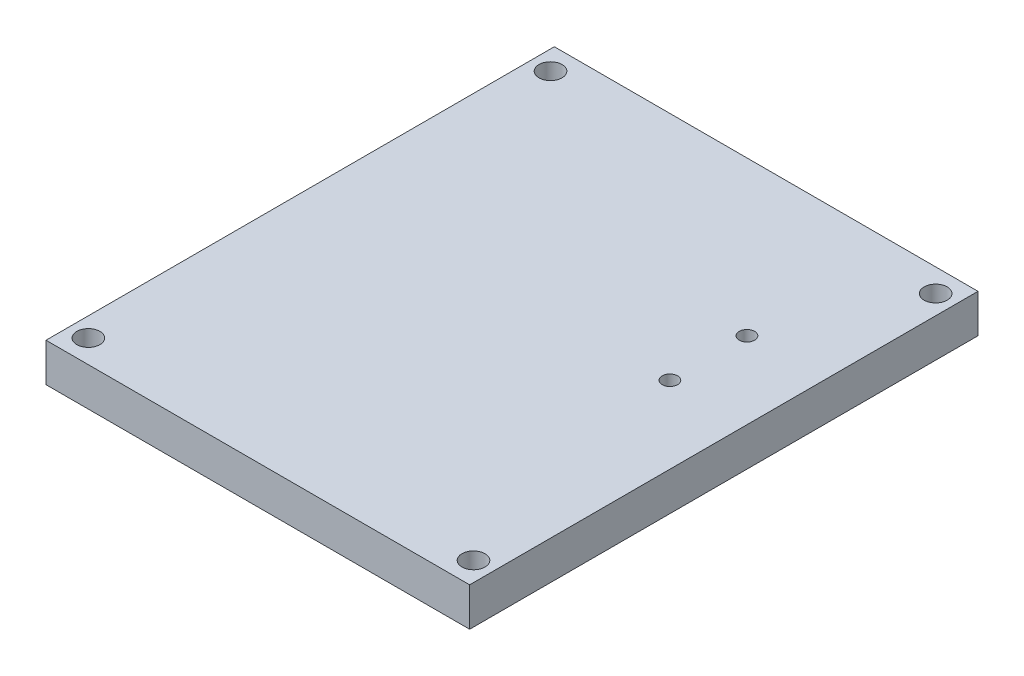
SolidWorks part; units mm, degrees
ref_plane "Plan de face" through (0, 0, 0) normal (0, 0, 1) x (1, 0, 0)
ref_plane "Plan de dessus" through (0, 0, 0) normal (0, 1, 0) x (1, 0, 0)
ref_plane "Plan de droite" through (0, 0, 0) normal (1, 0, 0) x (0, 0, -1)
sketch "Esquisse1" plane through (0, 0, 0) normal (0, 1, 0) x (1, 0, 0)
  line L0 (-27.5396, -33.0827) -> (27.4604, -33.0827)
  line L1 (-27.5396, -33.0827) -> (-27.5396, 32.9173)
  line L2 (-27.5396, 32.9173) -> (27.4604, 32.9173)
  line L3 (27.4604, -33.0827) -> (27.4604, 32.9173)
  line L4 (-27.5396, -33.0827) -> (27.4604, 32.9173) construction
  line L5 (-27.5396, 32.9173) -> (27.4604, -33.0827) construction
  line L6 (-25.0396, -30.0827) -> (24.9604, 29.9173) construction
  line L7 (-25.0396, 29.9173) -> (24.9604, -30.0827) construction
  line L8 (27.4604, 12.9173) -> (17.4604, 12.9173) construction
  line L9 (17.4604, 12.9173) -> (17.4604, 2.9173) construction
  line L10 (27.4604, 32.9173) -> (27.4604, 12.9173) construction
  circle A0 centre (-25.0396, 29.9173) radius 1.5
  circle A1 centre (24.9604, 29.9173) radius 1.5
  circle A2 centre (24.9604, -30.0827) radius 1.5
  circle A3 centre (-25.0396, -30.0827) radius 1.5
  circle A4 centre (17.4604, 12.9173) radius 1
  circle A5 centre (17.4604, 2.9173) radius 1
  point P0 (-0.0396, -0.0827)
  point P5 (-0.0396, -0.0827)
  dimension "D1" = 10
  dimension "D2" = 20
extrude "Boss.-Extru.1" add sketch "Esquisse1" along normal blind 5
